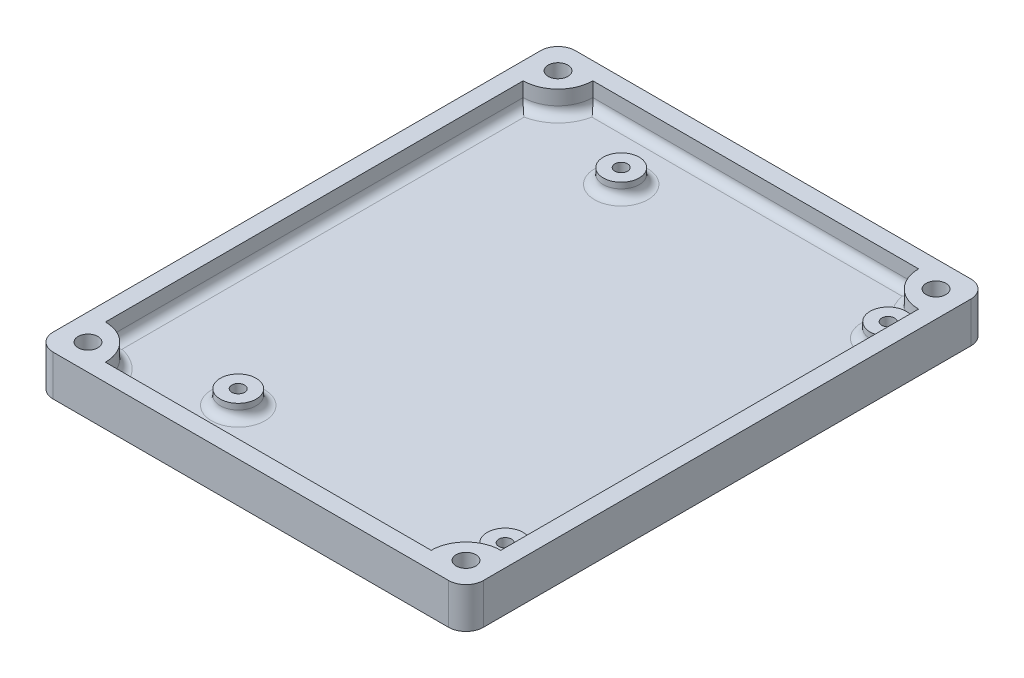
SolidWorks part; units mm, degrees
ref_plane "Front Plane" through (0, 0, 0) normal (0, 0, 1) x (1, 0, 0)
ref_plane "Top Plane" through (0, 0, 0) normal (0, 1, 0) x (1, 0, 0)
ref_plane "Right Plane" through (0, 0, 0) normal (1, 0, 0) x (0, 0, -1)
sketch "Sketch1" plane through (0, 0, 0) normal (0, 1, 0) x (1, 0, 0)
  line L1 (-76.8533, 114.959) -> (-2.7112, 114.959)
  line L2 (-76.8533, 114.959) -> (-76.8533, 24.959)
  line L3 (-76.8533, 24.959) -> (-2.7112, 24.959)
  line L4 (-2.7112, 114.959) -> (-2.7112, 24.959)
  line L5 (-76.8533, 114.959) -> (-2.7112, 24.959) construction
  line L6 (-76.8533, 24.959) -> (-2.7112, 114.959) construction
  line L8 (-76.8533, 111.959) -> (-76.8533, 27.959) construction
  line L9 (-2.7112, 24.959) -> (-76.8533, 24.959) construction
  line L10 (-2.7112, 114.959) -> (-2.7112, 24.959) construction
  line L11 (-2.7112, 114.959) -> (-76.8533, 114.959) construction
  point P0 (0, 0)
  point P6 (0, 0)
  point P7 (-43.0257, 8.6154)
  point P8 (76.0262, -67.7595)
  point P9 (59.2893, 32.2644)
  point P10 (-26.2319, 8.6154)
  point P11 (0, 0)
extrude "Boss-Extrude1" add sketch "Sketch1" along normal blind 3
sketch "Sketch2" plane through (0, 3, 0) normal (0, 1, 0) x (1, 0, 0)
  line L4 (-2.7112, 24.959) -> (-2.7112, 114.959)
  line L5 (-2.7112, 114.959) -> (-76.8533, 114.959)
  line L6 (-76.8533, 114.959) -> (-76.8533, 24.959)
  line L7 (-76.8533, 24.959) -> (-2.7112, 24.959)
  line L8 (-2.7112, 24.959) -> (-2.7112, 114.959)
  line L9 (-2.7112, 114.959) -> (-76.8533, 114.959)
  line L10 (-76.8533, 114.959) -> (-76.8533, 24.959)
  line L11 (-76.8533, 24.959) -> (-2.7112, 24.959)
  line L16 (-5.7112, 27.959) -> (-5.7112, 111.959)
  line L17 (-73.8533, 27.959) -> (-5.7112, 27.959)
  line L18 (-73.8533, 111.959) -> (-73.8533, 27.959)
  line L19 (-5.7112, 111.959) -> (-73.8533, 111.959)
  line L20 (-5.7112, 33.959) -> (-5.7112, 105.959)
  line L21 (-67.8533, 27.959) -> (-11.7112, 27.959)
  line L22 (-73.8533, 105.959) -> (-73.8533, 33.959)
  line L23 (-11.7112, 111.959) -> (-67.8533, 111.959)
  arc A1 (-73.8533, 105.959) -> (-67.8533, 111.959) centre (-73.8533, 111.959) ccw
  arc A2 (-67.8533, 27.959) -> (-73.8533, 33.959) centre (-73.8533, 27.959) ccw
  arc A3 (-11.7112, 111.959) -> (-5.7112, 105.959) centre (-5.7112, 111.959) ccw
  arc A5 (-5.7112, 33.959) -> (-11.7112, 27.959) centre (-5.7112, 27.959) ccw
  dimension "D3" = 12
  dimension "D1" = 0
  dimension "D2" = 3
extrude "Boss-Extrude2" add sketch "Sketch2" along normal blind 4
hole_wizard "CBORE for M3 SHCS1" positions "Sketch3" profile "Sketch4" counterbore size "M3" standard "ANSI Metric" end condition through all
sketch "Sketch3" plane through (0, 0, 0) normal (0, -1, 0) x (-1, 0, 0)
  line L0 (76.8533, 24.959) -> (2.7112, 24.959) construction
  line L1 (76.8533, 114.959) -> (76.8533, 24.959) construction
  line L2 (2.7112, 24.959) -> (2.7112, 114.959) construction
  line L3 (2.7112, 114.959) -> (76.8533, 114.959) construction
  point P0 (72.3533, 29.459)
  point P2 (7.2112, 29.459)
  point P4 (7.2112, 110.459)
  point P6 (72.3533, 110.459)
  point P9 (0, 0)
  point P10 (0, 0)
  point P11 (0, 0)
  point P12 (0, 0)
  dimension "D1" = 4.5
  dimension "D2" = 4.5
  dimension "D3" = 4.5
  dimension "D4" = 4.5
sketch "Sketch4" plane through (-72.3533, 0, -29.459) normal (1, 0, 0) x (0, 0, -1)
  line L0 (0, 0) -> (0, 7)
  line L1 (0, 7) -> (1.7, 7)
  line L3 (1.7, 7) -> (1.7, 4)
  line L4 (1.7, 4) -> (2.85, 4)
  line L5 (2.85, 4) -> (2.85, 0)
  line L7 (2.85, 0) -> (0, 0)
  line L11 (0, -6.35) -> (0, 107.95) construction
  dimension "Thru Hole Dia." = 3.4
  dimension "Thru Hole Depth" = 7
  dimension "C'Bore Dia." = 5.7
  dimension "C'Bore Depth" = 4
ref_plane "Plane1" through (-76.8533, 7, -114.959) normal (0, -1, 0) x (-1, 0, 0)
sketch "Sketch5" plane through (-76.8533, 7, -114.959) normal (0, -1, 0) x (1, 0, 0)
  line L1 (74.1421, 0) -> (0, 0) construction
  line L2 (71.1421, 81) -> (71.1421, 9) construction
  circle A0 centre (22.8921, 12) radius 3.1
  circle A1 centre (68.8921, 12) radius 3.1
  circle A2 centre (68.8921, 78) radius 3.1
  circle A3 centre (22.8921, 78) radius 3.1
  circle A4 centre (68.8921, 12) radius 1.1
  circle A5 centre (22.8921, 12) radius 1.1
  circle A6 centre (22.8921, 78) radius 1.1
  circle A7 centre (68.8921, 78) radius 1.1
  point P12 (0, 0)
  point P13 (0, 0)
  point P14 (55.8222, 14.7251)
  point P15 (63.3346, 13.8376)
  point P18 (0, 0)
  dimension "D1" = 2
  dimension "D2" = 2.2
  dimension "D3" = 66
  dimension "D4" = 46
  dimension "D5" = 12
  dimension "D6" = 2.25
extrude "Boss-Extrude8" add sketch "Sketch5" along normal up to surface (4 mm away) from offset 1.5 up to face at (-39.7822, 3, -69.959)
sketch "Sketch6" plane through (0, 3, 0) normal (0, 1, 0) x (1, 0, 0)
  circle A0 centre (-7.9612, 36.959) radius 1.1 construction
  circle A1 centre (-53.9612, 36.959) radius 1.1 construction
  circle A2 centre (-53.9612, 102.959) radius 1.1 construction
  circle A3 centre (-7.9612, 102.959) radius 1.1 construction
  circle A4 centre (-7.9612, 36.959) radius 1.1
  circle A5 centre (-53.9612, 36.959) radius 1.1
  circle A6 centre (-53.9612, 102.959) radius 1.1
  circle A7 centre (-7.9612, 102.959) radius 1.1
extrude "Cut-Extrude1" cut sketch "Sketch6" against normal blind 1.5
sketch "Sketch7" plane through (0, 7, 0) normal (0, 1, 0) x (1, 0, 0)
  line L0 (-67.8533, 27.959) -> (-11.7112, 27.959) construction
  line L1 (-15.7112, 27.959) -> (-19.2112, 27.959)
  line L2 (-15.7112, 27.959) -> (-15.7112, 24.959)
  line L3 (-15.7112, 24.959) -> (-19.2112, 24.959)
  line L4 (-19.2112, 27.959) -> (-19.2112, 24.959)
  line L5 (-76.8533, 24.959) -> (-2.7112, 24.959) construction
  line L6 (-2.7112, 24.959) -> (-2.7112, 114.959) construction
  dimension "D1" = 3.5
  dimension "D2" = 13
extrude "Cut-Extrude2" [suppressed] cut sketch "Sketch7" against normal blind 3.5
fillet "Fillet1" radius 1.5 12 edges at (-69.6107, 3, -32.2016) (-53.9612, 3, -33.859) (-9.9538, 3, -32.2016) (-11.0612, 3, -36.959) (-5.7112, 3, -69.959) (-11.0612, 3, -102.959) (-9.9538, 3, -107.7164) (-73.8533, 3, -69.959) (-69.6107, 3, -107.7164) (-39.7822, 3, -111.959) (-53.9612, 3, -99.859) (-39.7822, 3, -27.959)
fillet "Fillet2" radius 3 4 edges at (-2.7112, 3.5, -24.959) (-76.8533, 3.5, -24.959) (-76.8533, 3.5, -114.959) (-2.7112, 3.5, -114.959)
